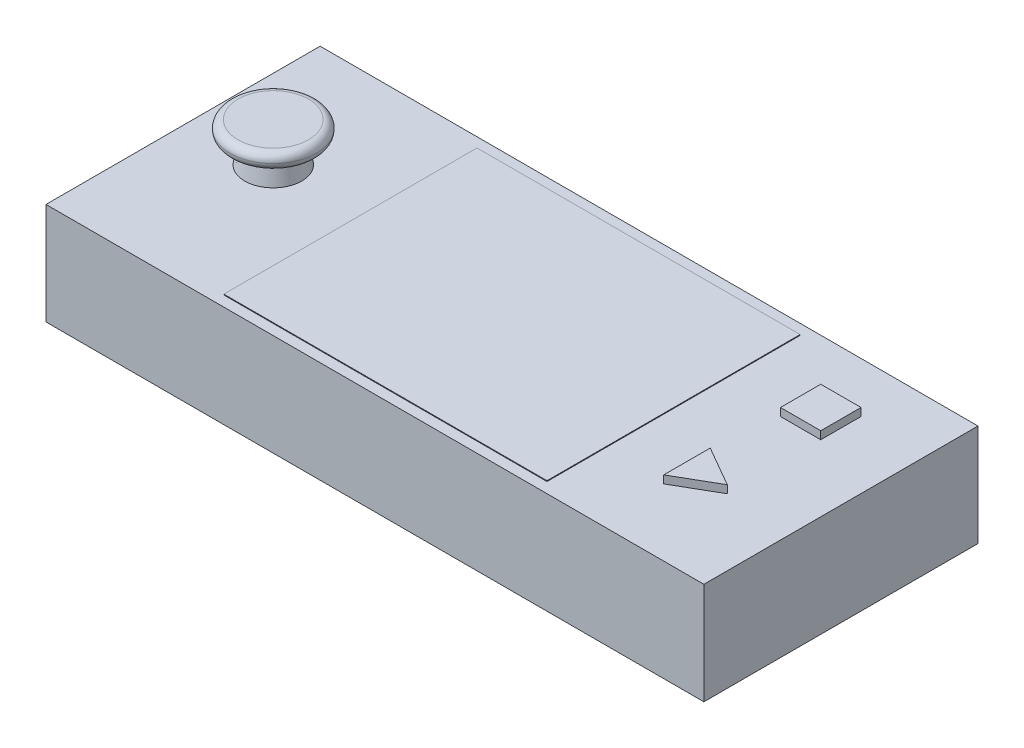
SolidWorks part; units mm, degrees
ref_plane "前视基准面" through (0, 0, 0) normal (0, 0, 1) x (1, 0, 0)
ref_plane "上视基准面" through (0, 0, 0) normal (0, 1, 0) x (1, 0, 0)
ref_plane "右视基准面" through (0, 0, 0) normal (1, 0, 0) x (0, 0, -1)
other "Configuration Table"
sketch "草图1" plane through (0, 0, 0) normal (0, 1, 0) x (1, 0, 0)
  line L1 (-42, -17.5) -> (42, -17.5)
  line L2 (-42, -17.5) -> (-42, 17.5)
  line L3 (-42, 17.5) -> (42, 17.5)
  line L4 (42, -17.5) -> (42, 17.5)
  line L5 (-42, -17.5) -> (42, 17.5) construction
  line L6 (-42, 17.5) -> (42, -17.5) construction
  point P0 (0, 0)
  dimension "D1" = 84
  dimension "D2" = 35
extrude "凸台-拉伸1" add sketch "草图1" along normal blind 13
sketch "草图2" plane through (0, 13, 0) normal (0, 1, 0) x (1, 0, 0)
  line L1 (28.3415, 11.0795) -> (33.4833, 11.0795)
  line L2 (28.3415, 11.0795) -> (28.3415, 5.9376)
  line L3 (28.3415, 5.9376) -> (33.4833, 5.9376)
  line L4 (33.4833, 11.0795) -> (33.4833, 5.9376)
  line L5 (28.3415, 11.0795) -> (33.4833, 5.9376) construction
  line L6 (28.3415, 5.9376) -> (33.4833, 11.0795) construction
  line L7 (33.4833, -5.9988) -> (28.3415, -3.0302)
  line L8 (28.3415, -3.0302) -> (28.3415, -8.9675)
  line L9 (28.3415, -8.9675) -> (33.4833, -5.9988)
  line L10 (-20.6287, -16.1602) -> (20.6287, -16.1602)
  line L11 (-20.6287, -16.1602) -> (-20.6287, 16.1602)
  line L12 (-20.6287, 16.1602) -> (20.6287, 16.1602)
  line L13 (20.6287, -16.1602) -> (20.6287, 16.1602)
  line L14 (-20.6287, -16.1602) -> (20.6287, 16.1602) construction
  line L15 (-20.6287, 16.1602) -> (20.6287, -16.1602) construction
  circle A0 centre (-31.8918, 1.4079) radius 3.6369
  circle A1 centre (30.0554, -5.9988) radius 1.714 construction
  point P2 (30.9124, 8.5086)
  point P20 (0, 0)
extrude "凸台-拉伸2" add sketch "草图2" along normal blind 3 draft 10 contours A0 region at (-31.8918, 13, -1.4079)
extrude "凸台-拉伸3" add sketch "草图2<3>" along normal blind 1 contours L4 L1 L2 L3 | L8 L9 L7 region at (30.9124, 13, -8.5086) region at (30.0554, 13, 5.9988)
sketch "草图2<3>" plane through (0, 13, 0) normal (0, 1, 0) x (1, 0, 0) same geometry as "草图2"
extrude "凸台-拉伸4" add sketch "草图2<4>" along normal blind 0.1 contours L10 L13 L12 L11 region at (0, 13, 0)
sketch "草图2<4>" plane through (0, 13, 0) normal (0, 1, 0) x (1, 0, 0) same geometry as "草图2"
sketch "草图4" plane through (0, 16, 0) normal (0, 1, 0) x (1, 0, 0)
  circle A0 centre (-31.8918, 1.4079) radius 5.5
  circle A1 centre (-31.8918, 1.4079) radius 3.1079 construction
  dimension "D1" = 11
extrude "凸台-拉伸5" add sketch "草图4" along normal blind 2
fillet "圆角1" radius 1 2 edges at (-31.8918, 16, 4.0921) (-31.8918, 18, 4.0921)
sketch "草图5" plane through (0, 0, 0) normal (0, -1, 0) x (1, 0, 0)
  line L0 (-42, 0) -> (42, 0) construction
  line L1 (16.5, 10) -> (25.5, 10)
  line L2 (16.5, 10) -> (16.5, -10)
  line L3 (16.5, -10) -> (25.5, -10)
  line L4 (25.5, 10) -> (25.5, -10)
  line L5 (16.5, 10) -> (25.5, -10) construction
  line L6 (16.5, -10) -> (25.5, 10) construction
  line L7 (-42, -17.5) -> (-42, 17.5) construction
  line L8 (42, 17.5) -> (42, -17.5) construction
  circle A0 centre (-38, 8) radius 2
  circle A1 centre (-38, -8) radius 2
  circle A2 centre (10, 8) radius 2
  circle A3 centre (10, -8) radius 2
  point P8 (21, 0)
  dimension "D2" = 4
  dimension "D3" = 4
  dimension "D4" = 4
  dimension "D5" = 16
  dimension "D6" = 48
  dimension "D1" = 4
  dimension "D7" = 20
  dimension "D8" = 9
  dimension "D9" = 16.5
extrude "切除-拉伸1" cut sketch "草图5" against normal blind 6
equation "\"D2@草图5\"=\"D1@草图5\""
equation "\"D3@草图5\"=\"D1@草图5\""
equation "\"D4@草图5\"=\"D1@草图5\""
